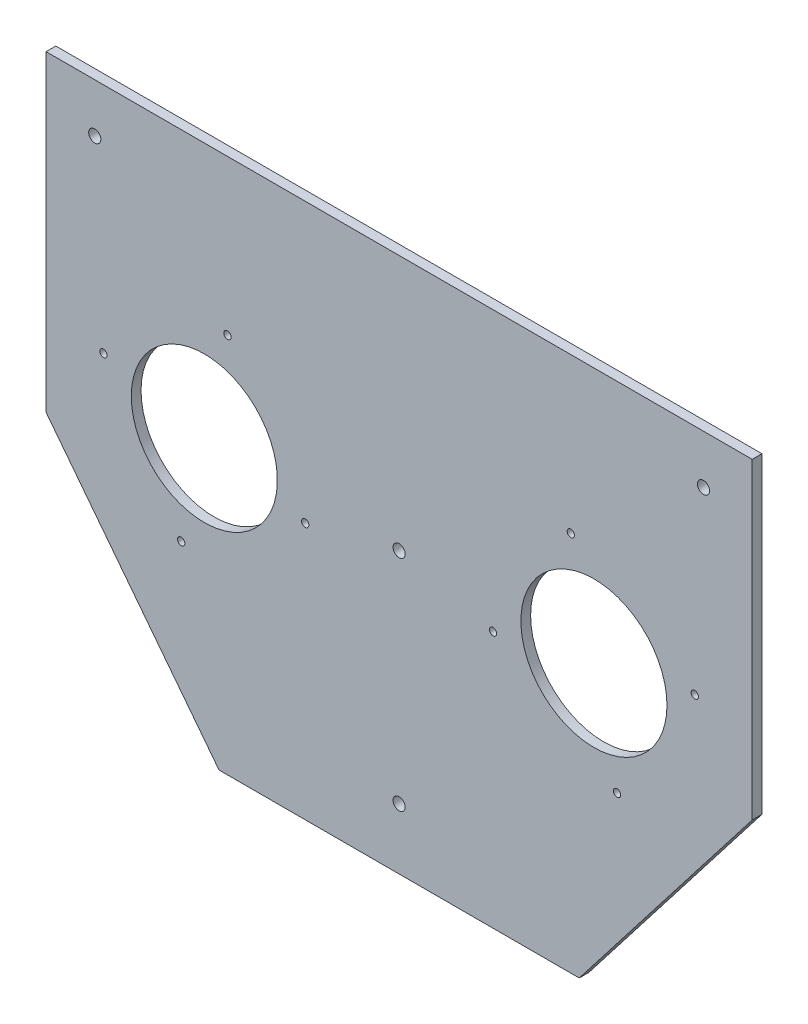
SolidWorks part; units mm, degrees
ref_plane "Front Plane" through (0, 0, 0) normal (0, 0, 1) x (1, 0, 0)
ref_plane "Top Plane" through (0, 0, 0) normal (0, 1, 0) x (1, 0, 0)
ref_plane "Right Plane" through (0, 0, 0) normal (1, 0, 0) x (0, 0, -1)
sketch "Sketch1" plane through (0, 0, 0) normal (0, 0, 1) x (1, 0, 0)
  line L0 (-125, 100) -> (125, 100) construction
  line L1 (-125, 0) -> (125, 0) construction
  line L2 (-145, -8.2843) -> (-73.9647, -100)
  line L3 (-73.9647, -100) -> (73.9647, -100)
  line L4 (73.9647, -100) -> (145, -8.2843)
  line L6 (0, -100) -> (0, 100) construction
  line L7 (-145, 120) -> (145, 120)
  line L8 (145, 120) -> (145, -8.2843)
  line L11 (-145, -8.2843) -> (-145, 120)
  circle A0 centre (-125, 100) radius 12.5 construction
  circle A10 centre (-125, 0) radius 12.5 construction
  circle A11 centre (125, 0) radius 12.5 construction
  circle A12 centre (-125, 0) radius 17.5 construction
  circle A13 centre (-125, 100) radius 17.5 construction
  circle A21 centre (-125, 100) radius 2.5
  circle A22 centre (125, 100) radius 2.5
  circle A24 centre (0, -75) radius 2.5
  point P12 (0, 100)
  point P45 (0, 120)
  dimension "D1" = 25
  dimension "D2" = 5
  dimension "D3" = 5
  dimension "D4" = 100
  dimension "D6" = 5
  dimension "D9" = 250
  dimension "D11" = 20
  dimension "D12" = 20
  dimension "D5" = 25
extrude "Boss-Extrude1" add sketch "Sketch1" along normal blind 4
sketch "Sketch2" plane through (0, 0, 4) normal (0, 0, 1) x (1, 0, 0)
  line L0 (121.4264, 24.4924) -> (38.5736, 5.5076) construction
  line L1 (89.4924, -26.4264) -> (70.5076, 56.4264) construction
  line L2 (0, 0) -> (0, 96.4486) construction
  line L3 (145, 120) -> (-145, 120) construction
  line L4 (-145, 120) -> (-145, -8.2843) construction
  line L5 (-80, 15) -> (80, 15) construction
  circle A0 centre (80, 15) radius 42.5 construction
  circle A1 centre (38.5736, 5.5076) radius 1.5
  circle A2 centre (70.5076, 56.4264) radius 1.5
  circle A3 centre (121.4264, 24.4924) radius 1.5
  circle A4 centre (89.4924, -26.4264) radius 1.5
  circle A5 centre (80, 15) radius 30
  circle A6 centre (-38.5736, 5.5076) radius 1.5
  circle A7 centre (-70.5076, 56.4264) radius 1.5
  circle A8 centre (-89.4924, -26.4264) radius 1.5
  circle A9 centre (-121.4264, 24.4924) radius 1.5
  circle A10 centre (-80, 15) radius 42.5 construction
  circle A11 centre (-80, 15) radius 30
  circle A12 centre (-80, 15) radius 47.5 construction
  circle A13 centre (0, 15) radius 2.5
  point P6 (80, 15)
  point P27 (-80, 15)
  dimension "D1" = 85
  dimension "D2" = 3
  dimension "D3" = 60
  dimension "D4" = 95
  dimension "D5" = 5
  dimension "D6" = 105
  dimension "D7" = 65
extrude "Cut-Extrude1" cut sketch "Sketch2" against normal blind 10
equation "\"D1@Sketch1\" = \"cf_tube_outer_diameter\""
equation "\"D9@Sketch1\"= \"mid_plate_horizontal_spacing\""
equation "\"mid_plate_mid_to_top\" = 100mm"
equation "\"mid_plate_mid_to_bottom\" = 125mm"
equation "\"mid_plate_horizontal_spacing\" = 250mm"
equation "\"cf_tube_outer_diameter\" = 25mm"
equation "\"D4@Sketch1\"=\"mid_plate_mid_to_top\""
equation "\"cf_tube_inner_diameter\" = 21mm"
equation "\"mid_tube_length\" = 500mm"
equation "\"cf_plate_thickness\" = 4mm"
equation "\"D1@Boss-Extrude1\"=\"cf_plate_thickness\""
